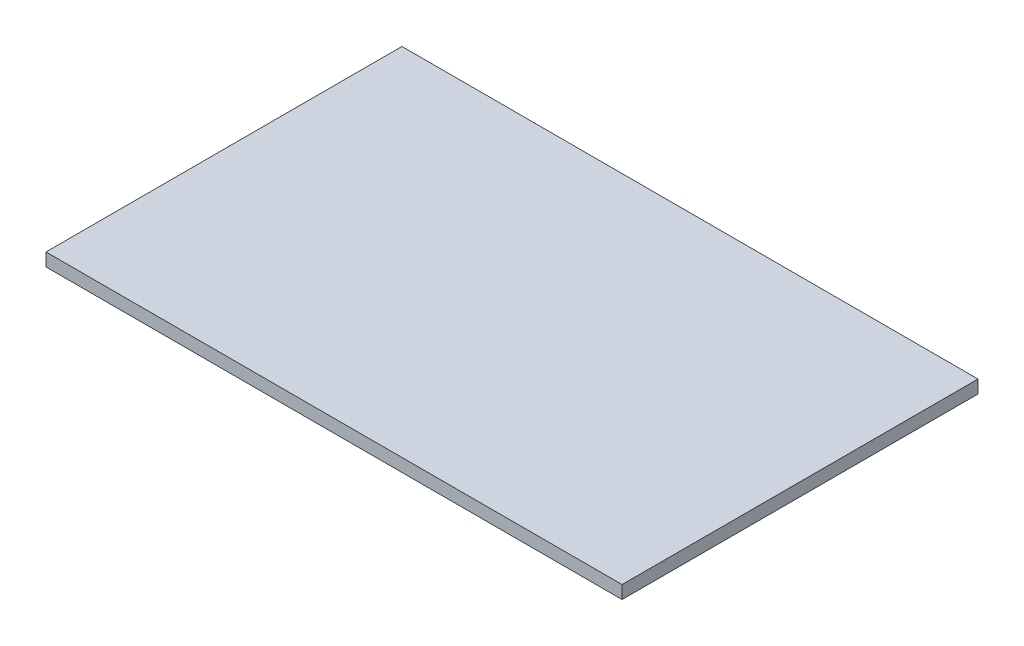
SolidWorks part; units mm, degrees
material "Glass"
ref_plane "Front Plane" through (0, 0, 0) normal (0, 0, 1) x (1, 0, 0)
ref_plane "Top Plane" through (0, 0, 0) normal (0, 1, 0) x (1, 0, 0)
ref_plane "Right Plane" through (0, 0, 0) normal (1, 0, 0) x (0, 0, -1)
sketch "Sketch1" plane through (0, 0, 0) normal (0, 1, 0) x (1, 0, 0)
  line L0 (0, 37.0077) -> (0, -43.1852) construction
  line L1 (57.5422, 0) -> (-54.911, 0) construction
  line L3 (44.5008, 27.4955) -> (-44.5008, 27.4955)
  line L4 (44.5008, 27.4955) -> (44.5008, -27.4955)
  line L5 (44.5008, -27.4955) -> (-44.5008, -27.4955)
  line L6 (-44.5008, 27.4955) -> (-44.5008, -27.4955)
  line L7 (44.5008, 27.4955) -> (-44.5008, -27.4955) construction
  line L8 (44.5008, -27.4955) -> (-44.5008, 27.4955) construction
  point P5 (0, 0)
  dimension "D1" = 89.0016
  dimension "D2" = 54.991
extrude "Boss-Extrude1" add sketch "Sketch1" along normal blind 2.0066
